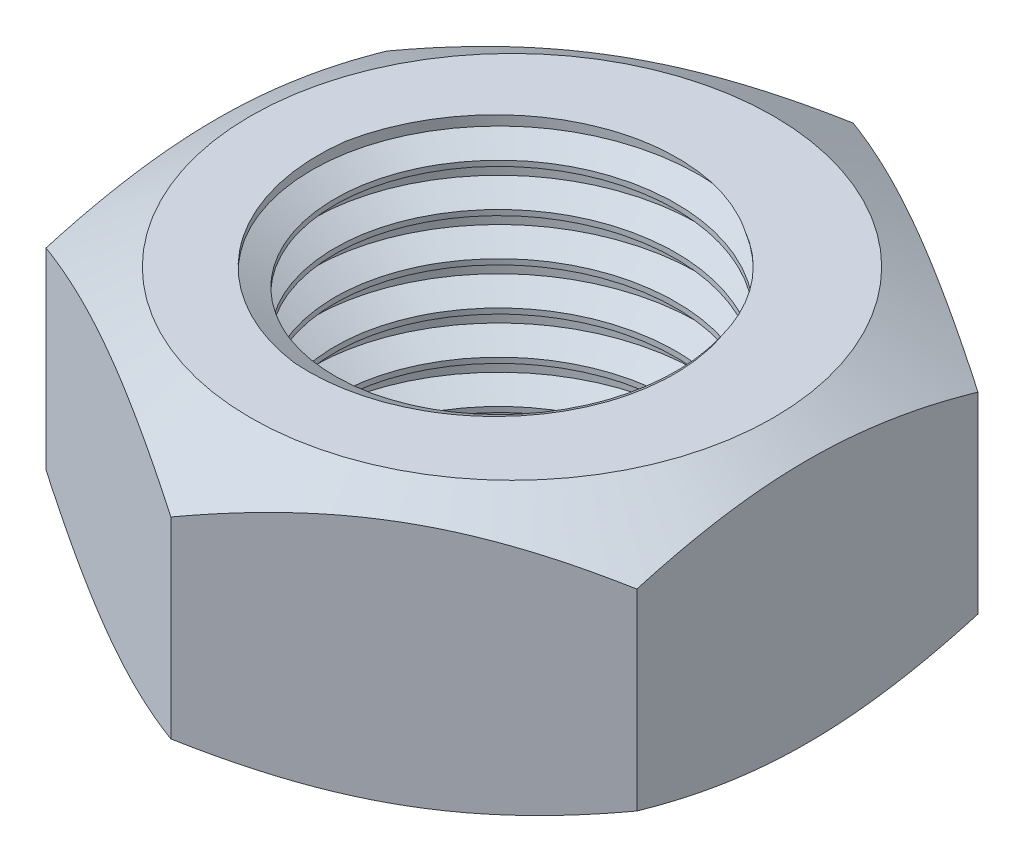
SolidWorks part; units mm, degrees
ref_plane "Front Plane" through (0, 0, 0) normal (0, 0, 1) x (1, 0, 0)
ref_plane "Top Plane" through (0, 0, 0) normal (0, 1, 0) x (1, 0, 0)
ref_plane "Right Plane" through (0, 0, 0) normal (1, 0, 0) x (0, 0, -1)
sketch "Sketch1" plane through (0, 0, 0) normal (0, 1, 0) x (1, 0, 0)
  line L1 (10.3923, 6) -> (0, 12)
  line L2 (0, 12) -> (-10.3923, 6)
  line L3 (-10.3923, 6) -> (-10.3923, -6)
  line L4 (-10.3923, -6) -> (0, -12)
  line L5 (0, -12) -> (10.3923, -6)
  line L6 (10.3923, -6) -> (10.3923, 6)
  circle A0 centre (0, 0) radius 6
  circle A1 centre (0, 0) radius 10.3923 construction
  point P3 (0, 0)
  dimension "D1" = 12
  dimension "D2" = 24
extrude "Boss-Extrude1" add sketch "Sketch1" along normal mid plane 10
thread "Thread1" pitch 1.5 method cut profile "Thread Profile1" start angle 0, offset 2, length 27, pitch 1.5, diameter 12
ref_plane "Plane1" through (-6, 7, 0) normal (0, 0, -1) x (1, 0, 0)
sketch "Thread Profile1" plane through (-6, 7, 0) normal (0, 0, -1) x (1, 0, 0)
  line L0 (0, 0) -> (0, 1.5) construction
  line L11 (0, 0) -> (0, 1.3125)
  line L12 (0, 1.3125) -> (-0.8119, 0.8437)
  line L13 (-0.8119, 0.8437) -> (-0.8119, 0.4687)
  line L15 (-0.8119, 0.4687) -> (0, 0)
  line L17 (-0.8119, 0.6562) -> (0, 0.6562) construction
  point P2 (0, 0)
  dimension "Pitch" = 1.5
  dimension "Profile_Angle" = 60
  dimension "Profile_Land" = 0.375
  dimension "Profile_Height" = 0.8119
sketch "Sketch5" plane through (0, 0, 0) normal (1, 0, 0) x (0, 0, -1)
  line L0 (0, 0) -> (0, 4.4079) construction
  line L3 (12, 5) -> (12, -5) construction
  line L4 (12, 3.3808) -> (12, 5)
  line L5 (12, 5) -> (9.1955, 5)
  line L6 (6, 5) -> (12, 5) construction
  line L7 (9.1955, 5) -> (12, 3.3808)
  dimension "D1" = 30
revolve "Cut-Revolve4" cut sketch "Sketch5" angle 360 about L0
mirror "Mirror1" about plane through (0, 0, 0) normal (0, 1, 0) of "Cut-Revolve4"
